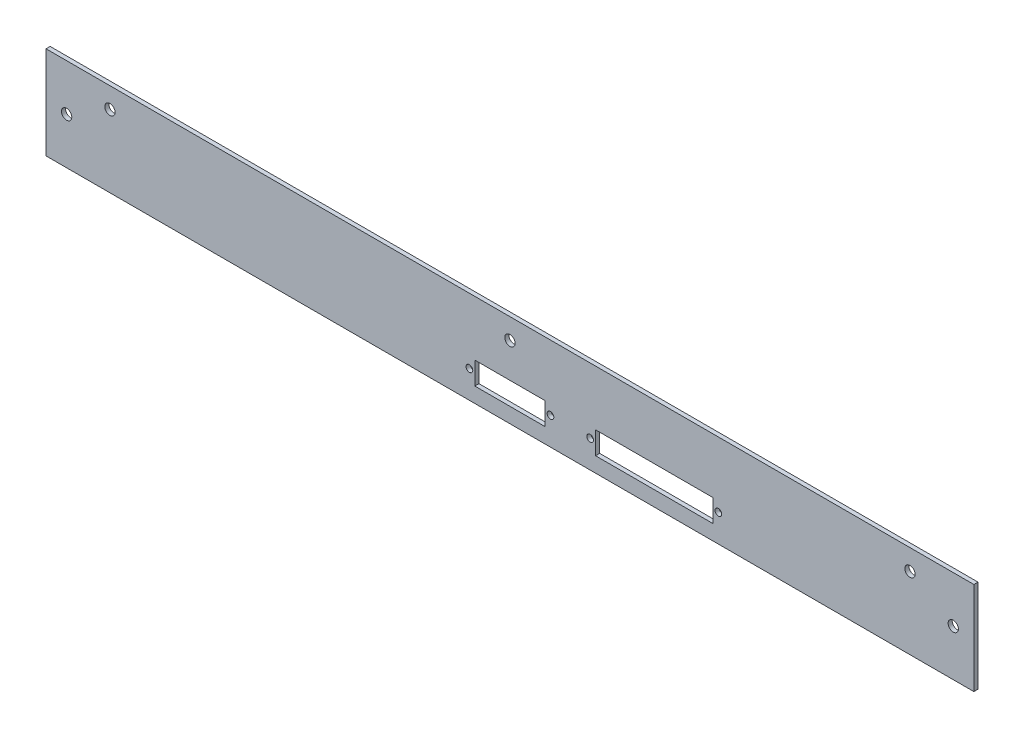
SolidWorks part; units mm, degrees
material "1345 Alloy"
ref_plane "Front Plane" through (0, 0, 0) normal (0, 0, 1) x (1, 0, 0)
ref_plane "Top Plane" through (0, 0, 0) normal (0, 1, 0) x (1, 0, 0)
ref_plane "Right Plane" through (0, 0, 0) normal (1, 0, 0) x (0, 0, -1)
sketch "Sketch1" plane through (0, 0, 0) normal (0, 0, 1) x (1, 0, 0)
  line L1 (-225, 22.5) -> (225, 22.5)
  line L2 (-225, 22.5) -> (-225, -22.5)
  line L3 (-225, -22.5) -> (225, -22.5)
  line L4 (225, 22.5) -> (225, -22.5)
  line L5 (-225, 22.5) -> (225, -22.5) construction
  line L6 (-225, -22.5) -> (225, 22.5) construction
  point P0 (0, 0)
  dimension "D1" = 450
  dimension "D2" = 45
extrude "Boss-Extrude1" add sketch "Sketch1" along normal blind 2
sketch "SK Terminal 06P cutout" plane through (0, 0, 0) normal (0, 0, 1) x (1, 0, 0)
  line L0 (-17.03, -15.175) -> (17.03, -15.175)
  line L1 (17.03, -15.175) -> (17.03, -4.275)
  line L2 (17.03, -4.275) -> (-17.03, -4.275)
  line L3 (-17.03, -4.275) -> (-17.03, -15.175)
  circle A0 centre (-19.655, -9.125) radius 1.625
  circle A1 centre (19.655, -9.125) radius 1.625
extrude "Terminal 06P cutout" cut sketch "SK Terminal 06P cutout" against normal through all and the other way through all
sketch "SK Terminal 12P cutout" plane through (0, 0, 0) normal (0, 0, 1) x (1, 0, 0)
  line L0 (41.54, -15.175) -> (98.46, -15.175)
  line L1 (98.46, -15.175) -> (98.46, -4.275)
  line L2 (98.46, -4.275) -> (41.54, -4.275)
  line L3 (41.54, -4.275) -> (41.54, -15.175)
  circle A0 centre (38.915, -9.125) radius 1.625
  circle A1 centre (101.085, -9.125) radius 1.625
extrude "Terminal 12P cutout" cut sketch "SK Terminal 12P cutout" against normal through all and the other way through all
sketch "Sketch2" plane through (0, 0, 2) normal (0, 0, 1) x (1, 0, 0)
  line L0 (-225, 22.5) -> (-215, 22.5) construction
  line L1 (-215, 22.5) -> (-215, 0) construction
  line L2 (-194, 12.4954) -> (194, 12.4954) construction
  line L3 (0, 22.5) -> (0, 12.5) construction
  circle A0 centre (-215, 0) radius 2.5
  circle A1 centre (215, 0) radius 2.5
  circle A2 centre (-194, 12.4954) radius 2.5
  circle A3 centre (194, 12.4954) radius 2.5
  circle A4 centre (0, 12.5) radius 2.5
  dimension "D3" = 5
  dimension "D4" = 5
  dimension "D5" = 5
  dimension "D7" = 5
  dimension "D8" = 5
  dimension "D1" = 10
  dimension "D2" = 22.5
  dimension "D6" = 10
extrude "Cut-Extrude1" cut sketch "Sketch2" against normal through all
